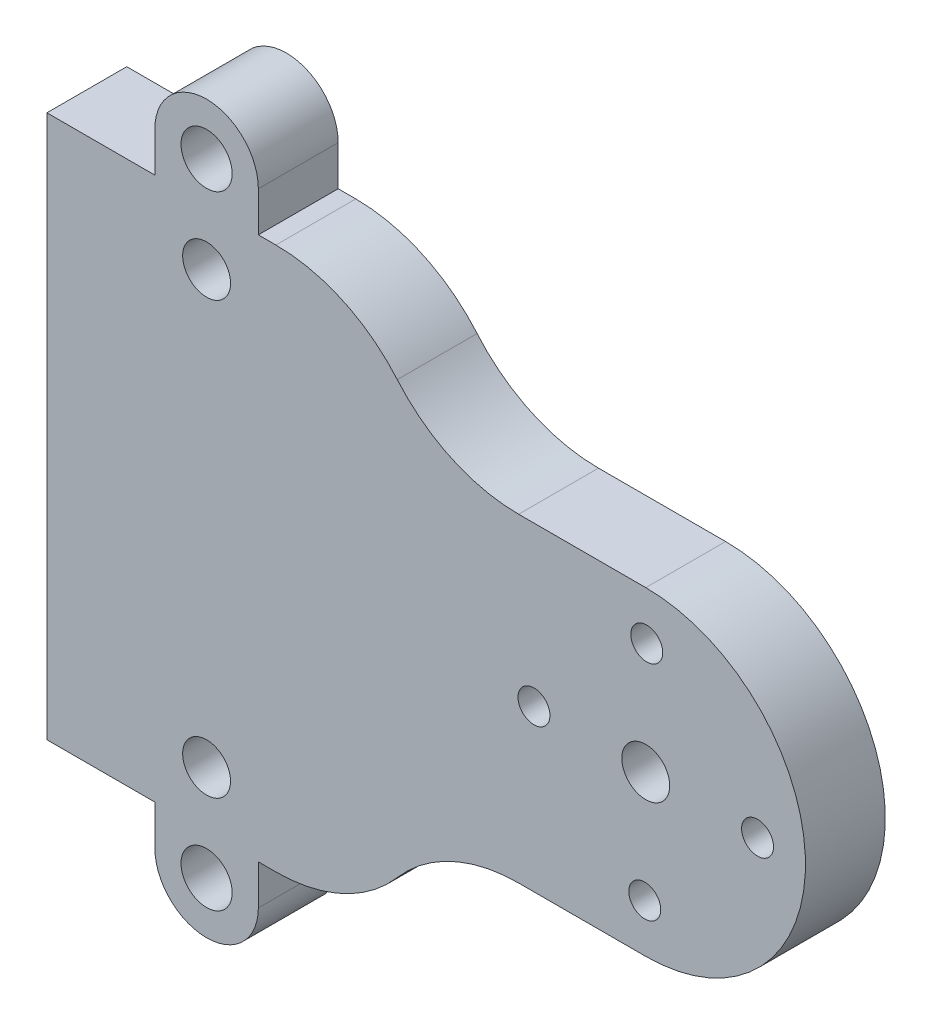
SolidWorks part; units mm, degrees
ref_plane "Plan de face" through (0, 0, 0) normal (0, 0, 1) x (1, 0, 0)
ref_plane "Plan de dessus" through (0, 0, 0) normal (0, 1, 0) x (1, 0, 0)
ref_plane "Plan de droite" through (0, 0, 0) normal (1, 0, 0) x (0, 0, -1)
sketch "Esquisse1" plane through (0, 0, 0) normal (0, 0, 1) x (1, 0, 0)
  line L0 (-13.5846, -30.0471) -> (-13.5846, -25.5471)
  line L1 (-13.8346, -25.2971) -> (-16.3346, -25.2971)
  line L2 (-16.5846, -25.0471) -> (-16.5846, 6.4529)
  line L3 (-16.3346, 6.7029) -> (-13.8346, 6.7029)
  line L4 (-13.5846, 6.9529) -> (-13.5846, 11.4529)
  line L5 (-13.3346, 11.7029) -> (-8.5846, 11.7029)
  line L6 (-8.5846, 11.7029) -> (-8.5846, 6.7029)
  line L7 (-8.5846, 6.7029) -> (-7.4918, 6.7029)
  line L8 (-7.4918, 6.7029) -> (-4.0345, 6.7029)
  line L9 (-4.0345, -25.2971) -> (-7.4918, -25.2971)
  line L10 (-7.4918, -25.2971) -> (-8.5846, -25.2971)
  line L11 (-8.5846, -25.2971) -> (-8.5846, -30.2971)
  line L12 (-8.5846, -30.2971) -> (-13.3346, -30.2971)
  line L13 (-13.3346, -30.2971) -> (-13.5846, -30.2971)
  line L14 (-13.5846, -30.2971) -> (-13.5846, -30.0471)
  line L15 (-13.5846, -25.5471) -> (-13.5846, -25.2971)
  line L16 (-13.5846, -25.2971) -> (-13.8346, -25.2971)
  line L17 (-16.3346, -25.2971) -> (-16.5846, -25.2971)
  line L18 (-16.5846, -25.2971) -> (-16.5846, -25.0471)
  line L19 (-16.3346, 6.7029) -> (-16.5846, 6.7029)
  line L20 (-16.5846, 6.7029) -> (-16.5846, 6.4529)
  line L21 (-13.5846, 6.9529) -> (-13.5846, 6.7029)
  line L22 (-13.5846, 6.7029) -> (-13.8346, 6.7029)
  line L23 (-13.5846, 11.4529) -> (-13.5846, 11.7029)
  line L24 (-13.5846, 11.7029) -> (-13.3346, 11.7029)
  arc A0 (3.4488, 4.7029) -> (-4.0345, 6.7029) centre (-4.0345, -8.2971) ccw
  arc A1 (3.4488, 4.7029) -> (18.4154, 0.7029) centre (18.4154, 30.7029) ccw
  arc A2 (18.4154, -19.2971) -> (18.4154, 0.7029) centre (18.4154, -9.2971) ccw
  arc A3 (18.4154, -19.2971) -> (3.4488, -23.2971) centre (18.4154, -49.2971) ccw
  arc A4 (-4.0345, -25.2971) -> (3.4488, -23.2971) centre (-4.0345, -10.2971) ccw
  circle A5 centre (18.4779, -2.2971) radius 1
  circle A6 centre (25.4154, -9.3596) radius 1
  circle A7 centre (18.4154, -9.2971) radius 1.5
  circle A8 centre (11.4154, -9.2347) radius 1
  circle A9 centre (18.3529, -16.2971) radius 1
extrude "Boss.-Extru.1" add sketch "Esquisse1" along normal blind 5
sketch "Esquisse2" plane through (0, 0, 0) normal (0, 0, -1) x (-1, 0, 0)
  line L0 (-18.4154, -9.2971) -> (7.3764, -9.2971) construction
  line L2 (1.5846, -19.2971) -> (1.5846, -26.2971) construction
  line L3 (4.0345, 6.7029) -> (8.5846, 6.7029) construction
  line L4 (1.5846, -19.2971) -> (1.5846, -25.2971)
  line L5 (-26.8332, -33.657) -> (-26.1987, -19.2971)
  line L6 (21.5846, -33.657) -> (-26.8332, -33.657)
  line L7 (21.5846, 7.7029) -> (1.5846, 7.7029)
  line L8 (21.5846, -26.2971) -> (21.5846, -33.657)
  line L9 (1.5846, 6.7029) -> (1.5846, 7.7029)
  line L10 (-26.1987, -19.2971) -> (1.5846, -19.2971)
  line L11 (1.5846, -25.2971) -> (1.5846, -26.2971)
  line L12 (-26.1987, 0.7029) -> (1.5846, 0.7029)
  line L13 (21.5846, -26.2971) -> (1.5846, -26.2971)
  line L15 (21.5846, 7.7029) -> (21.5846, 15.0627)
  line L16 (21.5846, 15.0627) -> (-26.8332, 15.0627)
  line L17 (-26.8332, 15.0627) -> (-26.1987, 0.7029)
  line L18 (1.5846, 0.7029) -> (1.5846, 7.7029) construction
  line L19 (1.5846, 0.7029) -> (1.5846, 6.7029)
  arc A1 (-18.4154, 0.7029) -> (-18.4154, -19.2971) centre (-18.4154, -9.2971) ccw construction
extrude "Enlèv. mat.-Extru.1" cut sketch "Esquisse2" against normal blind 5
sketch "Esquisse3" plane through (0, 0, 0) normal (0, 0, -1) x (-1, 0, 0)
  line L0 (8.5846, 7.7029) -> (13.5846, 7.7029) construction
  line L1 (21.5846, -26.2971) -> (1.5846, -26.2971)
  line L2 (21.5846, -26.2971) -> (21.5846, 7.7029)
  line L3 (21.5846, 7.7029) -> (1.5846, 7.7029)
  line L4 (1.5846, -26.2971) -> (1.5846, 7.7029)
  line L5 (13.5846, -26.2971) -> (8.5846, -26.2971) construction
  dimension "D1" = 0
  dimension "D2" = 20
  dimension "D3" = 0
extrude "Boss.-Extru.2" add sketch "Esquisse3" against normal blind 5
sketch "Esquisse4" plane through (0, 0, 0) normal (0, 0, -1) x (-1, 0, 0)
  line L1 (21.5846, -26.2971) -> (1.5846, -26.2971) construction
  line L2 (1.5846, -26.2971) -> (1.5846, -19.2971) construction
  line L4 (28.8831, -28.9494) -> (19.0846, -28.9494)
  line L5 (28.8831, -28.9494) -> (28.8831, 10.9087)
  line L6 (28.8831, 10.9087) -> (19.0846, 10.9087)
  line L7 (19.0846, -28.9494) -> (19.0846, 10.9087)
  circle A0 centre (9.0846, -22.7971) radius 1.5
  circle A1 centre (9.0846, 4.2029) radius 1.5
  dimension "D1" = 7.5
  dimension "D4" = 3
  dimension "D5" = 3
  dimension "D6" = 10
  dimension "D2" = 27
  dimension "D3" = 3.5
extrude "Enlèv. mat.-Extru.2" cut sketch "Esquisse4" against normal blind 5
sketch "Esquisse5" plane through (0, 0, 0) normal (0, 0, -1) x (-1, 0, 0)
  line L1 (1.5846, -26.2971) -> (-0.9154, -26.2971)
  line L2 (1.5846, -26.2971) -> (1.5846, 7.7029)
  line L3 (1.5846, 7.7029) -> (-0.9154, 7.7029)
  line L4 (-0.9154, -26.2971) -> (-0.9154, 7.7029)
  circle A0 centre (9.0846, -22.7971) radius 1.5 construction
  dimension "D1" = 10
extrude "Boss.-Extru.3" add sketch "Esquisse5" against normal up to vertex (5 mm away) up to point (-1.5846, -26.2971, 5)
sketch "Esquisse6" plane through (0, 0, 0) normal (0, 0, -1) x (-1, 0, 0)
  line L0 (19.0846, -26.2971) -> (-0.9154, -26.2971) construction
  line L1 (-0.9154, 7.7029) -> (19.0846, 7.7029) construction
  line L2 (12.3246, -25.1248) -> (5.8446, -25.1248)
  line L4 (12.3246, -28.7971) -> (12.3246, -25.1248)
  line L6 (5.8446, -28.7971) -> (5.8446, -25.1248)
  line L7 (12.3246, 6.7577) -> (5.8446, 6.7577)
  line L8 (5.8446, 6.7577) -> (5.8446, 10.2029)
  line L9 (12.3246, 6.7577) -> (12.3246, 10.2029)
  circle A0 centre (9.0846, -28.7971) radius 1.6
  circle A1 centre (9.0846, 10.2029) radius 1.6
  arc A2 (5.8446, -28.7971) -> (12.3246, -28.7971) centre (9.0846, -28.7971) ccw
  arc A3 (12.3246, 10.2029) -> (5.8446, 10.2029) centre (9.0846, 10.2029) ccw
  circle A5 centre (9.0846, -22.7971) radius 1.5 construction
  dimension "D1" = 3.2
  dimension "D2" = 3.2
  dimension "D3" = 2.5
  dimension "D4" = 2.5
  dimension "D5" = 0
  dimension "D6" = 6.48
  dimension "D7" = 6.48
extrude "Boss.-Extru.4" add sketch "Esquisse6" against normal up to vertex (5 mm away) up to point (-19.0846, 7.7029, 5)
fillet "Congé1" radius 10 2 edges at (0.9154, 0.7029, 2.5) (0.9154, -19.2971, 2.5)
fillet "Congé2" radius 10 2 edges at (0.9154, -26.2971, 2.5) (0.9154, 7.7029, 2.5)
